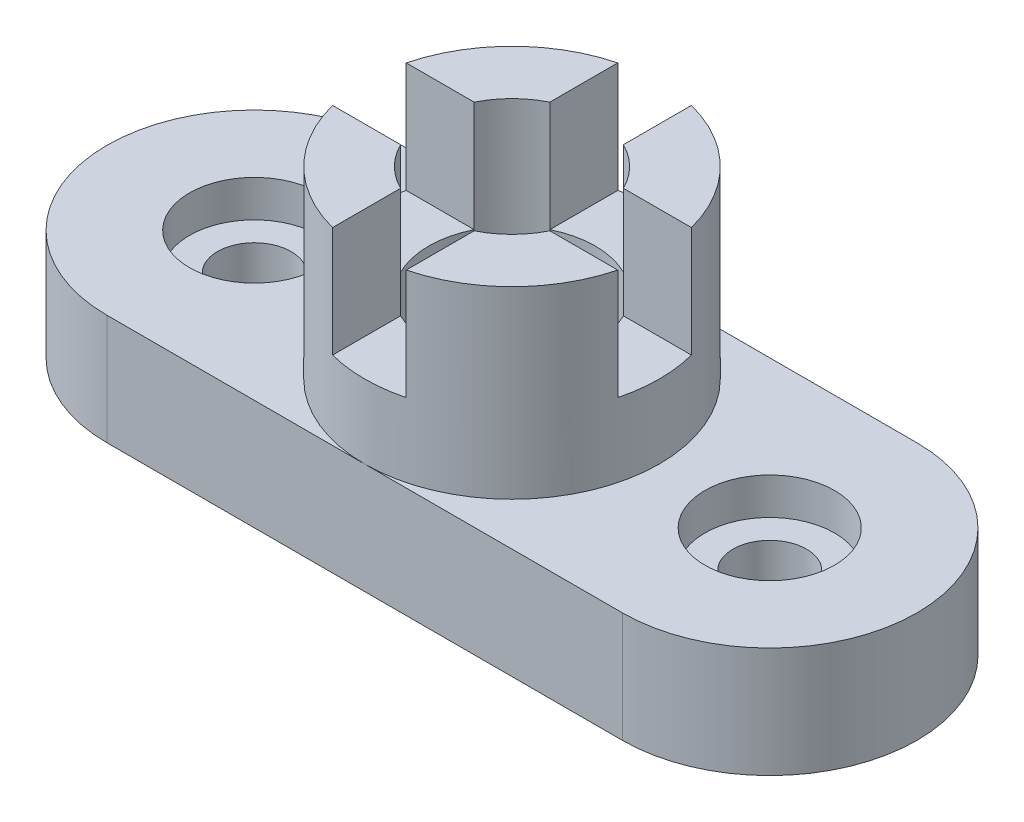
SolidWorks part; units mm, degrees
note: The reader was unsure of these and kept them because the rebuilt part matched: shared geometry of "Sketch1<3>", "Sketch1<4>", "Sketch1<5>".
ref_plane "Front Plane" through (0, 0, 0) normal (0, 0, 1) x (1, 0, 0)
ref_plane "Top Plane" through (0, 0, 0) normal (0, 1, 0) x (1, 0, 0)
ref_plane "Right Plane" through (0, 0, 0) normal (1, 0, 0) x (0, 0, -1)
sketch "Sketch1" plane through (0, 0, 0) normal (0, 1, 0) x (1, 0, 0)
  line L0 (-63.021, 0) -> (25.879, 0) construction
  line L1 (-63.021, 25.4) -> (25.879, 25.4)
  line L2 (-63.021, -25.4) -> (25.879, -25.4)
  line L3 (-24.921, 25.4) -> (-24.921, -25.4)
  line L4 (-12.221, 25.4) -> (-12.221, -25.4)
  line L5 (-43.1645, 6.35) -> (6.0224, 6.35)
  line L6 (-43.1645, -6.35) -> (6.0224, -6.35)
  arc A0 (-63.021, 25.4) -> (-63.021, -25.4) centre (-63.021, 0) ccw
  arc A1 (25.879, -25.4) -> (25.879, 25.4) centre (25.879, 0) ccw
  circle A2 centre (-63.021, 0) radius 11.176
  circle A3 centre (-63.021, 0) radius 6.35
  circle A4 centre (25.879, 0) radius 11.176
  circle A5 centre (25.879, 0) radius 6.35
  circle A6 centre (-18.571, 0) radius 25.4
  circle A7 centre (-18.571, 0) radius 14.351
  point P3 (-18.571, 0)
  dimension "D7" = 12.7
  dimension "D8" = 22.352
  dimension "D9" = 28.702
  dimension "D1" = 50.8
  dimension "D2" = 88.9
  dimension "D3" = 12.7
  dimension "D4" = 6.35
  dimension "D5" = 12.7
  dimension "D6" = 6.35
extrude "Boss-Extrude1" add sketch "Sketch1" along normal blind 19.05
extrude "Boss-Extrude2" add sketch "Sketch1<3>" along normal blind 50.8 contours A7 L3 A6 L5 | A7 L5 A6 L4 | A7 L6 A6 L3 | A7 L4 A6 L6
sketch "Sketch1<3>" plane through (0, 0, 0) normal (0, 1, 0) x (1, 0, 0) same geometry as "Sketch1"
extrude "Boss-Extrude3" add sketch "Sketch1<4>" along normal blind 31.75 contours A7 L4 A6 L3 | A6 L0 A7 L5 | A7 L0 A6 L5 | A7 L3 A6 L4 | L0 A6 L6 A7 | L0 A7 L6 A6
sketch "Sketch1<4>" plane through (0, 0, 0) normal (0, 1, 0) x (1, 0, 0) same geometry as "Sketch1"
extrude "Boss-Extrude4" add sketch "Sketch1<5>" along normal blind 12.7
sketch "Sketch1<5>" plane through (0, 0, 0) normal (0, 1, 0) x (1, 0, 0) same geometry as "Sketch1"
